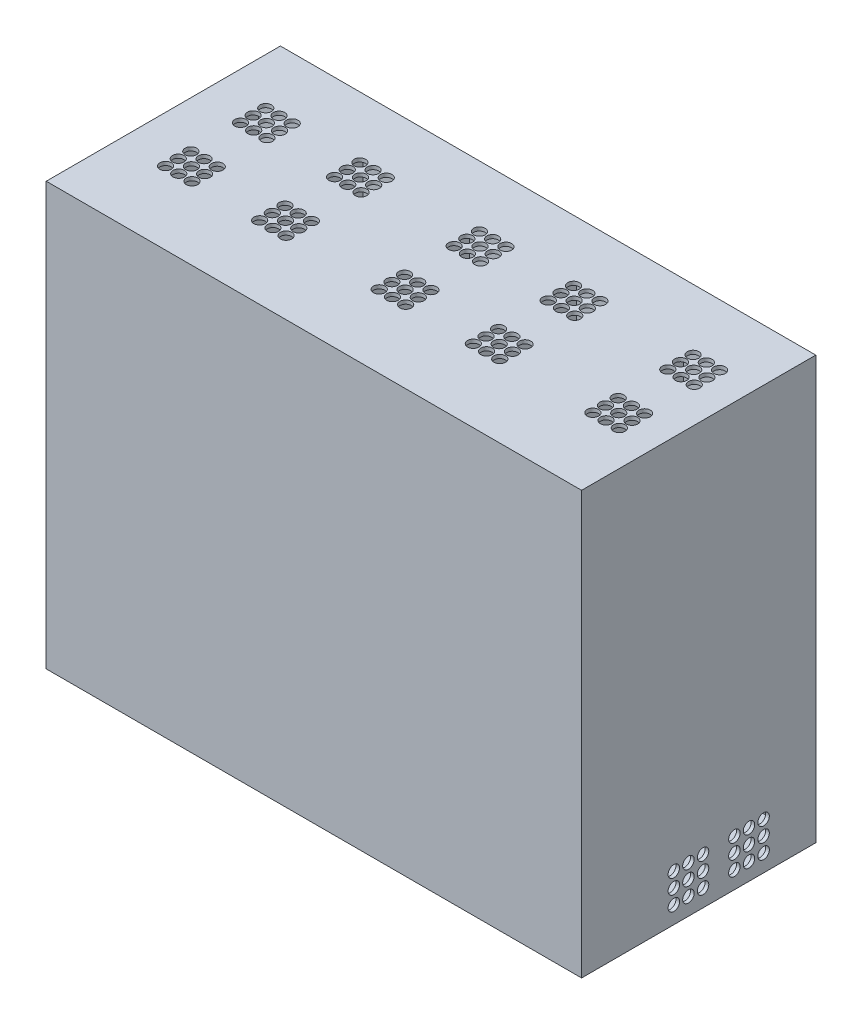
SolidWorks part; units mm, degrees
material "6061-T6 (SS)"
ref_plane "X-Y Datum" through (0, 0, 0) normal (0, 0, 1) x (1, 0, 0)
ref_plane "X-Z Datum" through (0, 0, 0) normal (0, 1, 0) x (1, 0, 0)
ref_plane "Y-Z Datum" through (0, 0, 0) normal (1, 0, 0) x (0, 0, -1)
sketch "Sketch1" plane through (0, 0, 0) normal (0, 0, 1) x (1, 0, 0)
  line L0 (-276.2265, 0) -> (276.2265, 0) construction
  line L1 (-276.2265, 154.041) -> (276.2265, 154.041)
  line L2 (-276.2265, 154.041) -> (-276.2265, -154.041)
  line L3 (-276.2265, -154.041) -> (276.2265, -154.041)
  line L4 (276.2265, 154.041) -> (276.2265, -154.041)
  line L5 (-276.2265, 154.041) -> (276.2265, -154.041) construction
  line L6 (-276.2265, -154.041) -> (276.2265, 154.041) construction
  line L7 (-275.2105, 153.025) -> (-189.6105, 153.025) construction
  line L8 (-275.2105, 153.025) -> (-275.2105, -153.025) construction
  line L9 (-275.2105, -153.025) -> (-189.6105, -153.025) construction
  line L10 (-189.6105, 153.025) -> (-189.6105, -153.025) construction
  line L11 (-275.2105, 153.025) -> (-189.6105, -153.025) construction
  line L12 (-275.2105, -153.025) -> (-189.6105, 153.025) construction
  line L13 (-188.5945, -154.041) -> (-188.5945, 154.041)
  line L14 (-279.4015, 157.216) -> (279.4015, 157.216)
  line L15 (279.4015, 157.216) -> (279.4015, -157.216)
  line L16 (-279.4015, -157.216) -> (279.4015, -157.216)
  line L17 (-279.4015, 157.216) -> (-279.4015, -157.216)
  line L18 (-185.4195, -154.041) -> (-185.4195, 154.041)
  line L19 (-188.5945, 0) -> (-185.4195, 0) construction
  line L20 (-182.2465, 153.025) -> (-182.2465, -153.025) construction
  line L21 (-182.2465, 153.025) -> (-96.6465, 153.025) construction
  line L22 (-96.6465, 153.025) -> (-96.6465, -153.025) construction
  line L23 (-182.2465, -153.025) -> (-96.6465, -153.025) construction
  line L24 (-95.6305, -154.041) -> (-95.6305, 154.041)
  line L25 (-92.4555, -154.041) -> (-92.4555, 154.041)
  line L26 (-89.2825, 153.025) -> (-89.2825, -153.025) construction
  line L27 (-89.2825, 153.025) -> (-3.6825, 153.025) construction
  line L28 (-3.6825, 153.025) -> (-3.6825, -153.025) construction
  line L29 (-89.2825, -153.025) -> (-3.6825, -153.025) construction
  line L30 (-2.6665, -154.041) -> (-2.6665, 154.041)
  line L31 (0.5085, -154.041) -> (0.5085, 154.041)
  line L32 (3.6815, 153.025) -> (3.6815, -153.025) construction
  line L33 (3.6815, 153.025) -> (89.2815, 153.025) construction
  line L34 (89.2815, 153.025) -> (89.2815, -153.025) construction
  line L35 (3.6815, -153.025) -> (89.2815, -153.025) construction
  line L36 (90.2975, -154.041) -> (90.2975, 154.041)
  line L37 (93.4725, -154.041) -> (93.4725, 154.041)
  line L38 (96.6455, 153.025) -> (96.6455, -153.025) construction
  line L39 (96.6455, 153.025) -> (182.2455, 153.025) construction
  line L40 (182.2455, 153.025) -> (182.2455, -153.025) construction
  line L41 (96.6455, -153.025) -> (182.2455, -153.025) construction
  line L42 (183.2615, -154.041) -> (183.2615, 154.041)
  line L43 (186.4365, -154.041) -> (186.4365, 154.041)
  line L44 (-182.2465, -153.025) -> (-96.6465, 153.025) construction
  line L45 (-182.2465, 153.025) -> (-96.6465, -153.025) construction
  line L46 (-89.2825, -153.025) -> (-3.6825, 153.025) construction
  line L47 (-89.2825, 153.025) -> (-3.6825, -153.025) construction
  line L48 (3.6815, -153.025) -> (89.2815, 153.025) construction
  line L49 (3.6815, 153.025) -> (89.2815, -153.025) construction
  line L50 (96.6455, -153.025) -> (182.2455, 153.025) construction
  line L51 (96.6455, 153.025) -> (182.2455, -153.025) construction
  line L52 (-276.2265, -157.216) -> (-276.2265, -208.016)
  line L53 (-279.4015, -157.216) -> (279.4015, -157.216)
  line L54 (-279.4015, -157.216) -> (-279.4015, -210.302)
  line L56 (279.4015, -157.216) -> (279.4015, -397.1906)
  line L58 (276.2265, -157.216) -> (276.2265, -392.7808)
  line L59 (186.4365, -154.041) -> (186.4365, -210.302)
  line L60 (183.2615, -157.216) -> (183.2615, -208.016)
  line L61 (186.4365, 154.041) -> (186.4365, 157.216)
  line L62 (-276.2265, -208.016) -> (276.2265, -392.7808) construction
  line L63 (-276.2265, -208.016) -> (183.2615, -208.016)
  line L64 (-279.4015, -210.302) -> (186.4365, -210.302)
  line L65 (-279.4015, -210.302) -> (279.4015, -397.1906) construction
  point P0 (0, 0)
  point P6 (-232.4105, 0)
  point P23 (-187.007, 0)
  point P24 (-139.4465, 0)
  dimension "D1" = 306.05
  dimension "D2" = 85.6
  dimension "D3" = 1.016
  dimension "D4" = 1.016
  dimension "D5" = 1.016
  dimension "D8" = 45.4035
  dimension "D10" = 89.789
  dimension "D12" = 92.964
  dimension "D13" = 89.79
  dimension "D14" = 50.8
  dimension "D16" = 2.286
  dimension "D6" = 3.175
  dimension "D7" = 3.175
  dimension "D15" = 3.175
  dimension "D9" = 5
  dimension "D11" = 5
extrude "Boss-Extrude1" add sketch "Sketch1" along normal blind 3.175 contours L3 L43 L1 L42 | L54 L64 L59 L53 L60 L63 L52 L16 | L52 L63 L60 L16 | L3 L42 L1 L37 | L3 L36 L1 L31 | L3 L31 L1 L30 | L3 L37 L1 L36 | L3 L30 L1 L25 | L1 L61 L14 L17 L16 L53 L59 L3 L2 | L3 L24 L1 L18 | L3 L13 L1 L2 | L3 L18 L1 L13 | L3 L25 L1 L24 region at (-276.7885, 0, 0) region at (-232.4105, 0, 0) region at (-187.007, 0, 0) region at (-140.525, 0, 0) region at (-94.043, 0, 0) region at (-47.561, 0, 0) region at (-1.079, 0, 0) region at (45.403, 0, 0) region at (91.885, 0, 0) region at (138.367, 0, 0) region at (184.849, 0, 0) region at (185.9676, -183.759, 0) region at (-46.4825, -182.616, 0)
sketch "Sketch2" plane through (0, 0, 3.175) normal (0, 0, 1) x (1, 0, 0)
  line L0 (-188.5945, -154.041) -> (-188.5945, 154.041) construction
  line L1 (-95.6305, -154.041) -> (-95.6305, 154.041) construction
  line L2 (-185.4195, -154.041) -> (-185.4195, 154.041) construction
  line L3 (90.2975, -154.041) -> (90.2975, 154.041) construction
  line L4 (276.2265, 154.041) -> (-276.2265, 154.041)
  line L5 (276.2265, -154.041) -> (276.2265, 154.041)
  line L6 (-276.2265, -154.041) -> (276.2265, -154.041)
  line L7 (-276.2265, 154.041) -> (-276.2265, -154.041)
  line L8 (276.2265, 154.041) -> (-276.2265, 154.041)
  line L9 (276.2265, -154.041) -> (276.2265, 154.041)
  line L10 (-276.2265, -154.041) -> (276.2265, -154.041)
  line L11 (-276.2265, 154.041) -> (-276.2265, -154.041)
  line L12 (-279.4015, -157.216) -> (279.4015, -157.216)
  line L13 (-279.4015, -157.216) -> (279.4015, -157.216) construction
  line L14 (279.4015, 157.216) -> (279.4015, -157.216) construction
  line L15 (-279.4015, 157.216) -> (279.4015, 157.216) construction
  line L16 (-279.4015, -157.216) -> (279.4015, -157.216)
  line L20 (0.5085, -154.041) -> (0.5085, 154.041) construction
  line L21 (-2.6665, -154.041) -> (-2.6665, 154.041) construction
  line L22 (-92.4555, -154.041) -> (-92.4555, 154.041) construction
  line L23 (186.4365, -154.041) -> (186.4365, 154.041) construction
  line L24 (183.2615, -154.041) -> (183.2615, 154.041) construction
  line L25 (93.4725, -154.041) -> (93.4725, 154.041) construction
  line L26 (-188.5945, -154.041) -> (-188.5945, 154.041)
  line L27 (-95.6305, -154.041) -> (-95.6305, 154.041)
  line L28 (-185.4195, -154.041) -> (-185.4195, 154.041)
  line L29 (90.2975, -154.041) -> (90.2975, 154.041)
  line L30 (0.5085, -154.041) -> (0.5085, 154.041)
  line L31 (-2.6665, -154.041) -> (-2.6665, 154.041)
  line L32 (-92.4555, -154.041) -> (-92.4555, 154.041)
  line L33 (186.4365, -154.041) -> (186.4365, 154.041)
  line L34 (183.2615, -154.041) -> (183.2615, 154.041)
  line L35 (93.4725, -154.041) -> (93.4725, 154.041)
  line L36 (-279.4015, 157.216) -> (-279.4015, -157.216) construction
  line L37 (-279.4015, -157.216) -> (279.4015, -157.216) construction
  line L38 (-279.4015, -157.216) -> (-279.4015, -210.302) construction
  line L41 (-276.2265, -157.216) -> (-276.2265, -208.016) construction
  line L44 (-276.2265, 154.041) -> (276.2265, 154.041) construction
  line L45 (276.2265, 154.041) -> (276.2265, -154.041) construction
  line L46 (-276.2265, -154.041) -> (276.2265, -154.041) construction
  line L47 (-276.2265, 154.041) -> (-276.2265, -154.041) construction
  line L48 (-188.5945, -154.041) -> (-188.5945, 154.041)
  line L49 (-95.6305, -154.041) -> (-95.6305, 154.041)
  line L50 (-185.4195, -154.041) -> (-185.4195, 154.041)
  line L51 (-279.4015, -157.216) -> (279.4015, -157.216)
  line L52 (279.4015, 157.216) -> (279.4015, -157.216)
  line L53 (-279.4015, 157.216) -> (279.4015, 157.216)
  line L54 (-279.4015, 157.216) -> (-279.4015, -157.216)
  line L55 (-279.4015, -157.216) -> (279.4015, -157.216)
  line L56 (-279.4015, -157.216) -> (-279.4015, -210.302)
  line L59 (90.2975, -154.041) -> (90.2975, 154.041)
  line L60 (0.5085, -154.041) -> (0.5085, 154.041)
  line L61 (-2.6665, -154.041) -> (-2.6665, 154.041)
  line L62 (-92.4555, -154.041) -> (-92.4555, 154.041)
  line L63 (186.4365, -154.041) -> (186.4365, 154.041)
  line L64 (183.2615, -154.041) -> (183.2615, 154.041)
  line L65 (93.4725, -154.041) -> (93.4725, 154.041)
  line L66 (-276.2265, -157.216) -> (-276.2265, -208.016)
  line L67 (-279.4015, -210.302) -> (186.4365, -210.302) construction
  line L69 (-276.2265, 154.041) -> (276.2265, 154.041)
  line L70 (276.2265, 154.041) -> (276.2265, -154.041)
  line L71 (-276.2265, -154.041) -> (276.2265, -154.041)
  line L72 (-276.2265, 154.041) -> (-276.2265, -154.041)
  line L73 (183.2615, -157.216) -> (183.2615, -208.016) construction
  line L74 (186.4365, 154.041) -> (186.4365, 157.216) construction
  line L75 (186.4365, -154.041) -> (186.4365, -210.302) construction
  line L76 (-188.5945, -154.041) -> (-188.5945, 154.041)
  line L77 (-95.6305, -154.041) -> (-95.6305, 154.041)
  line L78 (-185.4195, -154.041) -> (-185.4195, 154.041)
  line L79 (-279.4015, -157.216) -> (279.4015, -157.216)
  line L80 (279.4015, 157.216) -> (279.4015, -157.216)
  line L81 (-279.4015, 157.216) -> (279.4015, 157.216)
  line L82 (-279.4015, 157.216) -> (-279.4015, -157.216)
  line L83 (-279.4015, -157.216) -> (279.4015, -157.216)
  line L84 (-279.4015, -157.216) -> (-279.4015, -210.302)
  line L85 (-276.2265, -208.016) -> (183.2615, -208.016) construction
  line L87 (90.2975, -154.041) -> (90.2975, 154.041)
  line L88 (0.5085, -154.041) -> (0.5085, 154.041)
  line L89 (-2.6665, -154.041) -> (-2.6665, 154.041)
  line L90 (-92.4555, -154.041) -> (-92.4555, 154.041)
  line L91 (183.2615, -154.041) -> (183.2615, 154.041)
  line L92 (93.4725, -154.041) -> (93.4725, 154.041)
  line L93 (183.2615, -157.216) -> (183.2615, -208.016)
  line L94 (-276.2265, -157.216) -> (-276.2265, -208.016)
  line L97 (186.4365, 154.041) -> (186.4365, 157.216)
  line L98 (186.4365, -154.041) -> (186.4365, 154.041)
  line L99 (186.4365, -154.041) -> (186.4365, -210.302)
  line L100 (-276.2265, 154.041) -> (276.2265, 154.041)
  line L101 (276.2265, 154.041) -> (276.2265, -154.041)
  line L102 (-276.2265, -154.041) -> (276.2265, -154.041)
  line L103 (-276.2265, 154.041) -> (-276.2265, -154.041)
  line L104 (-188.5945, -154.041) -> (-188.5945, 154.041)
  line L106 (-95.6305, -154.041) -> (-95.6305, 154.041)
  line L107 (-185.4195, -154.041) -> (-185.4195, 154.041)
  line L108 (-279.4015, -157.216) -> (279.4015, -157.216)
  line L109 (279.4015, 157.216) -> (279.4015, -157.216)
  line L110 (-279.4015, 157.216) -> (279.4015, 157.216)
  line L111 (-279.4015, 157.216) -> (-279.4015, -157.216)
  line L112 (-279.4015, -157.216) -> (279.4015, -157.216)
  line L113 (186.4365, 154.041) -> (186.4365, 157.216)
  line L114 (186.4365, -154.041) -> (186.4365, 154.041)
  line L115 (186.4365, -154.041) -> (186.4365, -210.302)
  line L116 (-279.4015, -210.302) -> (186.4365, -210.302)
  line L117 (-279.4015, -157.216) -> (-279.4015, -210.302)
  line L118 (90.2975, -154.041) -> (90.2975, 154.041)
  line L119 (0.5085, -154.041) -> (0.5085, 154.041)
  line L120 (-2.6665, -154.041) -> (-2.6665, 154.041)
  line L121 (-92.4555, -154.041) -> (-92.4555, 154.041)
  line L122 (183.2615, -154.041) -> (183.2615, 154.041)
  line L123 (93.4725, -154.041) -> (93.4725, 154.041)
  line L124 (183.2615, -157.216) -> (183.2615, -208.016)
  line L125 (-276.2265, -208.016) -> (183.2615, -208.016)
  line L126 (-276.2265, -157.216) -> (-276.2265, -208.016)
  line L128 (-276.2265, 154.041) -> (276.2265, 154.041)
  line L129 (276.2265, 154.041) -> (276.2265, -154.041)
  line L130 (-276.2265, -154.041) -> (276.2265, -154.041)
  line L131 (-276.2265, 154.041) -> (-276.2265, -154.041)
  line M9 (186.4365, 157.216) -> (-279.4015, 157.216)
  line M10 (-279.4015, 157.216) -> (-279.4015, -210.302)
  line M86 (186.4365, -210.302) -> (186.4365, 157.216)
  line M120 (-279.4015, -210.302) -> (186.4365, -210.302)
  dimension "D1" = 0
  dimension "D2" = 0
extrude "Boss-Extrude2" add sketch "Sketch2" along normal blind 200.6 contours L125 L66 L16 L83 L93 M10 M120 M86 | L16 L55 L83 L10 L11 L8 M10 M86 M9 | L34 L10 L8 M86 | L10 L35 L8 L29 | L10 L28 L8 L26 | L10 L32 L8 L27 | L31 L10 L30 L8 region at (184.849, 0, 3.175) region at (184.849, 154.603, 3.175) region at (91.885, 0, 3.175) region at (185.9676, -183.759, 3.175) region at (-1.079, 0, 3.175) region at (-94.043, 0, 3.175) region at (-187.007, 0, 3.175)
sketch "Sketch11" plane through (0, 0, 203.775) normal (0, 0, 1) x (1, 0, 0)
  line L0 (-188.5945, -154.041) -> (-188.5945, 154.041) construction
  line L2 (-95.6305, -154.041) -> (-95.6305, 154.041) construction
  line L3 (-185.4195, -154.041) -> (-185.4195, 154.041) construction
  line L4 (186.4365, -210.302) -> (186.4365, 157.216)
  line L5 (186.4365, 157.216) -> (-279.4015, 157.216)
  line L6 (-279.4015, 157.216) -> (-279.4015, -210.302)
  line L7 (-279.4015, -210.302) -> (186.4365, -210.302)
  line L8 (186.4365, -210.302) -> (186.4365, 157.216)
  line L9 (186.4365, 157.216) -> (-279.4015, 157.216)
  line L10 (-279.4015, 157.216) -> (-279.4015, -210.302)
  line L11 (-279.4015, -210.302) -> (186.4365, -210.302)
  line L12 (-279.4015, -157.216) -> (279.4015, -157.216) construction
  line L14 (-279.4015, 157.216) -> (279.4015, 157.216) construction
  line L15 (-279.4015, 157.216) -> (-279.4015, -157.216) construction
  line L16 (-279.4015, -157.216) -> (279.4015, -157.216) construction
  line L17 (186.4365, 154.041) -> (186.4365, 157.216) construction
  line L18 (186.4365, -154.041) -> (186.4365, 154.041) construction
  line L19 (186.4365, -154.041) -> (186.4365, -210.302) construction
  line L20 (-279.4015, -210.302) -> (186.4365, -210.302) construction
  line L21 (-279.4015, -157.216) -> (-279.4015, -210.302) construction
  line L22 (90.2975, -154.041) -> (90.2975, 154.041) construction
  line L23 (0.5085, -154.041) -> (0.5085, 154.041) construction
  line L24 (-2.6665, -154.041) -> (-2.6665, 154.041) construction
  line L25 (-92.4555, -154.041) -> (-92.4555, 154.041) construction
  line L26 (183.2615, -154.041) -> (183.2615, 154.041) construction
  line L27 (93.4725, -154.041) -> (93.4725, 154.041) construction
  line L28 (183.2615, -157.216) -> (183.2615, -208.016) construction
  line L29 (-276.2265, -208.016) -> (183.2615, -208.016) construction
  line L30 (-276.2265, -157.216) -> (-276.2265, -208.016) construction
  line L32 (-276.2265, 154.041) -> (276.2265, 154.041) construction
  line L34 (-276.2265, -154.041) -> (276.2265, -154.041) construction
  line L35 (-276.2265, 154.041) -> (-276.2265, -154.041) construction
  line L36 (-188.5945, -154.041) -> (-188.5945, 154.041)
  line L37 (183.2615, -157.216) -> (183.2615, -154.041)
  line L38 (-95.6305, -154.041) -> (-95.6305, 154.041)
  line L39 (-185.4195, -154.041) -> (-185.4195, 154.041)
  line L40 (-279.4015, -157.216) -> (186.4365, -157.216)
  line L42 (-279.4015, 157.216) -> (186.4365, 157.216)
  line L43 (-279.4015, 157.216) -> (-279.4015, -157.216)
  line L44 (-279.4015, -157.216) -> (186.4365, -157.216)
  line L45 (186.4365, 154.041) -> (186.4365, 157.216)
  line L46 (186.4365, -154.041) -> (186.4365, 154.041)
  line L47 (186.4365, -154.041) -> (186.4365, -210.302)
  line L48 (-279.4015, -210.302) -> (186.4365, -210.302)
  line L49 (-279.4015, -157.216) -> (-279.4015, -210.302)
  line L50 (90.2975, -154.041) -> (90.2975, 154.041)
  line L51 (0.5085, -154.041) -> (0.5085, 154.041)
  line L52 (-2.6665, -154.041) -> (-2.6665, 154.041)
  line L53 (-92.4555, -154.041) -> (-92.4555, 154.041)
  line L54 (183.2615, -154.041) -> (183.2615, 154.041)
  line L55 (93.4725, -154.041) -> (93.4725, 154.041)
  line L56 (183.2615, -157.216) -> (183.2615, -208.016)
  line L57 (-276.2265, -208.016) -> (183.2615, -208.016)
  line L58 (-276.2265, -157.216) -> (-276.2265, -208.016)
  line L59 (-276.2265, -157.216) -> (-276.2265, -154.041)
  line L60 (-276.2265, 154.041) -> (186.4365, 154.041)
  line L62 (-276.2265, -154.041) -> (186.4365, -154.041)
  line L63 (-276.2265, 154.041) -> (-276.2265, -154.041)
  line M7 (-185.4195, 154.041) -> (-95.6305, 154.041)
  line M11 (-92.4555, 154.041) -> (-2.6665, 154.041)
  line M15 (0.5085, 154.041) -> (90.2975, 154.041)
  line M19 (93.4725, 154.041) -> (183.2615, 154.041)
  line M20 (183.2615, 154.041) -> (183.2615, -154.041)
  line M21 (186.4365, -210.302) -> (186.4365, 157.216)
  line M22 (186.4365, 157.216) -> (-279.4015, 157.216)
  line M23 (-279.4015, 157.216) -> (-279.4015, -210.302)
  line M24 (-279.4015, -210.302) -> (186.4365, -210.302)
  line M25 (-276.2265, -208.016) -> (-276.2265, -157.216)
  line M27 (183.2615, -157.216) -> (183.2615, -208.016)
  line M28 (183.2615, -208.016) -> (-276.2265, -208.016)
  line M31 (-276.2265, -154.041) -> (-276.2265, 154.041)
  line M32 (-276.2265, 154.041) -> (-188.5945, 154.041)
  dimension "D1" = 0
extrude "Boss-Extrude8" add sketch "Sketch11" along normal blind 64.05 contours L40 L10 M24 M21 M27 M28 M25 | L62 L60 M20 M21 | L62 L37 L40 L8 | L60 L40 L59 M32 M7 M11 M15 M19 M21 M22 M23 M31 region at (-46.4825, -209.8331, 203.775) region at (184.849, -155.6285, 203.775) region at (184.849, 0, 203.775) region at (-278.8395, 0, 203.775)
sketch "Sketch10" plane through (0, 0, 0) normal (0, 0, 1) x (1, 0, 0)
  line L1 (186.4365, 157.216) -> (220.4725, 157.216)
  line L2 (186.4365, 157.216) -> (186.4365, 61.966)
  line L3 (186.4365, 61.966) -> (220.4725, 61.966)
  line L4 (186.4365, -210.302) -> (186.4365, 157.216)
  line L5 (-279.4015, -210.302) -> (186.4365, -210.302)
  line L6 (-279.4015, 157.216) -> (-279.4015, -210.302)
  line L7 (186.4365, 157.216) -> (-279.4015, 157.216)
  line L8 (186.4365, -210.302) -> (186.4365, 157.216)
  line L10 (-279.4015, 157.216) -> (-279.4015, -210.302)
  line L11 (186.4365, 157.216) -> (-279.4015, 157.216)
  line L12 (220.4725, 157.216) -> (220.4725, 61.966)
  line L13 (-276.2265, -157.216) -> (183.2615, -157.216) construction
  line L14 (-276.2265, -157.216) -> (183.2615, -157.216)
  line L15 (186.4365, -157.216) -> (220.4725, -157.216)
  line L16 (186.4365, -157.216) -> (186.4365, -61.966)
  line L17 (186.4365, -61.966) -> (220.4725, -61.966)
  line L18 (220.4725, -157.216) -> (220.4725, -61.966)
  line L19 (186.4365, 157.216) -> (135.6365, 157.216)
  line L20 (186.4365, 157.216) -> (186.4365, 191.252)
  line L21 (186.4365, 191.252) -> (135.6365, 191.252)
  line L22 (135.6365, 157.216) -> (135.6365, 191.252)
  line L26 (-279.4015, -210.302) -> (186.4365, -210.302)
  dimension "D2" = 34.036
  dimension "D3" = 95.25
  dimension "D4" = 50.8
  dimension "D1" = 0
extrude "Boss-Extrude7" add sketch "Sketch10" along normal blind 3.175 contours L12 L1 L2 L3 | L15 L18 L17 L8 | L22 L11 L20 L21 region at (203.4545, 109.591, 0) region at (161.0365, 174.234, 0) region at (203.4545, -109.591, 0)
ref_plane "Plane1" through (-46.4825, 0, 0) normal (-1, 0, 0) x (0, 0, 1)
mirror "Mirror1" [suppressed] about plane through (-46.4825, 0, 0) normal (-1, 0, 0)
sketch "Sketch12" plane through (186.4365, 0, 0) normal (1, 0, 0) x (0, 0, -1)
  line L0 (-223.375, -210.302) -> (-267.825, -108.702)
  line L1 (-267.825, 93.716) -> (-242.425, 157.216)
  line L10 (0, -210.302) -> (0, -157.216)
  line L13 (0, -157.216) -> (-3.175, -157.216)
  line L14 (0, -157.216) -> (-3.175, -157.216)
  line L15 (-3.175, -157.216) -> (-3.175, -61.966)
  line L16 (-3.175, -157.216) -> (-3.175, -61.966)
  line L17 (-3.175, 157.216) -> (-267.825, 157.216)
  line L18 (-267.825, 157.216) -> (-267.825, -210.302)
  line L19 (-267.825, -210.302) -> (0, -210.302)
  line L20 (0, -210.302) -> (0, -157.216)
  line L27 (-3.175, 157.216) -> (-267.825, 157.216)
  line L28 (-267.825, 157.216) -> (-267.825, -210.302)
  line L29 (-267.825, -210.302) -> (0, -210.302)
  line L30 (-3.175, -61.966) -> (0, -61.966)
  line L31 (-3.175, -61.966) -> (0, -61.966)
  line L32 (0, -61.966) -> (0, 61.966)
  line L33 (0, -61.966) -> (0, 61.966)
  line L34 (0, 61.966) -> (-3.175, 61.966)
  line L35 (0, 61.966) -> (-3.175, 61.966)
  line L36 (-3.175, 61.966) -> (-3.175, 157.216)
  line L37 (-3.175, 61.966) -> (-3.175, 157.216)
  line M18 (-3.175, 157.216) -> (-267.825, 157.216)
  line M19 (-267.825, 157.216) -> (-267.825, -210.302)
  line M20 (-267.825, -210.302) -> (0, -210.302)
  dimension "D2" = 44.45
  dimension "D3" = 101.6
  dimension "D4" = 25.4
  dimension "D5" = 63.5
  dimension "D1" = 0
extrude "Cut-Extrude1" cut sketch "Sketch12" against normal through all contours L0 M20 M19 | L1 M19 M18 region at (186.4365, -176.4353, 253.0083) region at (186.4365, 136.0493, 259.3583)
sketch "Sketch13" plane through (0, 157.216, 0) normal (0, 1, 0) x (1, 0, 0)
  circle A0 centre (-238.9105, -118.4317) radius 5 construction
  circle A1 centre (-238.9105, -129.4317) radius 5 construction
  circle A2 centre (-238.9105, -140.4317) radius 5 construction
  circle A3 centre (-227.4105, -140.4317) radius 5 construction
  circle A4 centre (-227.4105, -129.4317) radius 5 construction
  circle A5 centre (-227.4105, -118.4317) radius 5 construction
  circle A6 centre (-215.9105, -118.4317) radius 5 construction
  circle A7 centre (-215.9105, -129.4317) radius 5 construction
  circle A8 centre (-215.9105, -140.4317) radius 5 construction
  circle A9 centre (-238.9105, -118.4317) radius 5
  circle A10 centre (-238.9105, -129.4317) radius 5
  circle A11 centre (-238.9105, -140.4317) radius 5
  circle A12 centre (-227.4105, -140.4317) radius 5
  circle A13 centre (-227.4105, -129.4317) radius 5
  circle A14 centre (-227.4105, -118.4317) radius 5
  circle A15 centre (-215.9105, -118.4317) radius 5
  circle A16 centre (-215.9105, -129.4317) radius 5
  circle A17 centre (-215.9105, -140.4317) radius 5
  circle A18 centre (-215.9105, -53.2317) radius 5 construction
  circle A19 centre (-215.9105, -53.2317) radius 5
  circle A20 centre (-215.9105, -75.2317) radius 5 construction
  circle A21 centre (-227.4105, -75.2317) radius 5 construction
  circle A22 centre (-238.9105, -75.2317) radius 5 construction
  circle A23 centre (-238.9105, -64.2317) radius 5 construction
  circle A24 centre (-227.4105, -64.2317) radius 5 construction
  circle A25 centre (-215.9105, -64.2317) radius 5 construction
  circle A26 centre (-227.4105, -53.2317) radius 5 construction
  circle A27 centre (-238.9105, -53.2317) radius 5 construction
  circle A28 centre (-215.9105, -75.2317) radius 5
  circle A29 centre (-227.4105, -75.2317) radius 5
  circle A30 centre (-238.9105, -75.2317) radius 5
  circle A31 centre (-238.9105, -64.2317) radius 5
  circle A32 centre (-227.4105, -64.2317) radius 5
  circle A33 centre (-215.9105, -64.2317) radius 5
  circle A34 centre (-215.9105, -53.2317) radius 5
  circle A35 centre (-227.4105, -53.2317) radius 5
  circle A36 centre (-238.9105, -53.2317) radius 5
  circle A37 centre (-145.525, -140.4317) radius 5 construction
  circle A38 centre (-145.525, -129.4317) radius 5 construction
  circle A39 centre (-145.525, -118.4317) radius 5 construction
  circle A40 centre (-157.025, -118.4317) radius 5 construction
  circle A41 centre (-157.025, -129.4317) radius 5 construction
  circle A42 centre (-157.025, -140.4317) radius 5 construction
  circle A43 centre (-145.525, -140.4317) radius 5
  circle A44 centre (-145.525, -129.4317) radius 5
  circle A45 centre (-145.525, -118.4317) radius 5
  circle A46 centre (-157.025, -118.4317) radius 5
  circle A47 centre (-157.025, -129.4317) radius 5
  circle A48 centre (-157.025, -140.4317) radius 5
  circle A49 centre (-134.025, -118.4317) radius 5 construction
  circle A50 centre (-134.025, -140.4317) radius 5 construction
  circle A51 centre (-134.025, -129.4317) radius 5 construction
  circle A52 centre (-134.025, -118.4317) radius 5
  circle A53 centre (-134.025, -140.4317) radius 5
  circle A54 centre (-134.025, -129.4317) radius 5
  circle A55 centre (-157.025, -75.2317) radius 5 construction
  circle A56 centre (-145.525, -75.2317) radius 5 construction
  circle A57 centre (-134.025, -75.2317) radius 5 construction
  circle A58 centre (-157.025, -75.2317) radius 5
  circle A59 centre (-145.525, -75.2317) radius 5
  circle A60 centre (-134.025, -75.2317) radius 5
  circle A61 centre (-134.025, -53.2317) radius 5 construction
  circle A62 centre (-145.525, -53.2317) radius 5 construction
  circle A63 centre (-157.025, -53.2317) radius 5 construction
  circle A64 centre (-157.025, -64.2317) radius 5 construction
  circle A65 centre (-134.025, -64.2317) radius 5 construction
  circle A66 centre (-145.525, -64.2317) radius 5 construction
  circle A67 centre (-134.025, -53.2317) radius 5
  circle A68 centre (-145.525, -53.2317) radius 5
  circle A69 centre (-157.025, -53.2317) radius 5
  circle A70 centre (-157.025, -64.2317) radius 5
  circle A71 centre (-134.025, -64.2317) radius 5
  circle A72 centre (-145.525, -64.2317) radius 5
extrude "Cut-Extrude2" cut sketch "Sketch13" against normal up to surface (3.175 mm away) contours A35 | A36 | A31 | A32 | A33 | A30 | A29 | A28 | A10 | A13 | A11 | A12 | A17 | A16 | A15 | A19 | A9 | A14 region at (-238.9105, 157.216, 129.4317) region at (-238.9105, 157.216, 140.4317) region at (-227.4105, 157.216, 140.4317) region at (-227.4105, 157.216, 129.4317) region at (-215.9105, 157.216, 118.4317) region at (-215.9105, 157.216, 129.4317) region at (-215.9105, 157.216, 140.4317) region at (-215.9105, 157.216, 75.2317) region at (-227.4105, 157.216, 75.2317) region at (-238.9105, 157.216, 75.2317) region at (-238.9105, 157.216, 64.2317) region at (-227.4105, 157.216, 64.2317) region at (-215.9105, 157.216, 64.2317) region at (-227.4105, 157.216, 53.2317) region at (-238.9105, 157.216, 53.2317) up to face at (-47.3453, 154.041, 107.467)
pattern_linear "LPattern1" count 3 spacing 185.92 along (1, 0, 0) of "Cut-Extrude2"
sketch "Sketch14" plane through (0, 157.216, 0) normal (0, 1, 0) x (1, 0, 0)
  circle A1 centre (-215.9105, -53.2317) radius 5
  circle A2 centre (-215.9105, -53.2317) radius 5
  circle A3 centre (-215.9105, -140.4317) radius 5
  circle A4 centre (-215.9105, -140.4317) radius 5
  circle A5 centre (-215.9105, -129.4317) radius 5
  circle A6 centre (-215.9105, -129.4317) radius 5
  circle A7 centre (-215.9105, -118.4317) radius 5
  circle A8 centre (-215.9105, -118.4317) radius 5
  circle A9 centre (-227.4105, -118.4317) radius 5
  circle A10 centre (-227.4105, -118.4317) radius 5
  circle A11 centre (-227.4105, -129.4317) radius 5
  circle A12 centre (-227.4105, -129.4317) radius 5
  circle A13 centre (-227.4105, -140.4317) radius 5
  circle A14 centre (-227.4105, -140.4317) radius 5
  circle A15 centre (-238.9105, -140.4317) radius 5
  circle A16 centre (-238.9105, -140.4317) radius 5
  circle A17 centre (-238.9105, -129.4317) radius 5
  circle A18 centre (-238.9105, -129.4317) radius 5
  circle A19 centre (-238.9105, -118.4317) radius 5
  circle A20 centre (-238.9105, -118.4317) radius 5
  circle A21 centre (-227.4105, -75.2317) radius 5
  circle A22 centre (-227.4105, -75.2317) radius 5
  circle A23 centre (-215.9105, -75.2317) radius 5
  circle A24 centre (-215.9105, -75.2317) radius 5
  circle A25 centre (-238.9105, -53.2317) radius 5
  circle A26 centre (-238.9105, -53.2317) radius 5
  circle A27 centre (-227.4105, -53.2317) radius 5
  circle A28 centre (-227.4105, -53.2317) radius 5
  circle A29 centre (-215.9105, -53.2317) radius 5
  circle A30 centre (-215.9105, -53.2317) radius 5
  circle A31 centre (-215.9105, -64.2317) radius 5
  circle A32 centre (-215.9105, -64.2317) radius 5
  circle A33 centre (-227.4105, -64.2317) radius 5
  circle A34 centre (-227.4105, -64.2317) radius 5
  circle A35 centre (-238.9105, -64.2317) radius 5
  circle A36 centre (-238.9105, -64.2317) radius 5
  circle A37 centre (-238.9105, -75.2317) radius 5
  circle A38 centre (-238.9105, -75.2317) radius 5
  circle A39 centre (-134.025, -118.4317) radius 5
  circle A40 centre (-134.025, -118.4317) radius 5
  circle A41 centre (-157.025, -140.4317) radius 5
  circle A42 centre (-157.025, -140.4317) radius 5
  circle A43 centre (-157.025, -129.4317) radius 5
  circle A44 centre (-157.025, -129.4317) radius 5
  circle A45 centre (-157.025, -118.4317) radius 5
  circle A46 centre (-157.025, -118.4317) radius 5
  circle A47 centre (-145.525, -118.4317) radius 5
  circle A48 centre (-145.525, -118.4317) radius 5
  circle A49 centre (-145.525, -129.4317) radius 5
  circle A50 centre (-145.525, -129.4317) radius 5
  circle A51 centre (-145.525, -140.4317) radius 5
  circle A52 centre (-145.525, -140.4317) radius 5
  circle A53 centre (-134.025, -75.2317) radius 5
  circle A54 centre (-134.025, -75.2317) radius 5
  circle A55 centre (-145.525, -75.2317) radius 5
  circle A56 centre (-145.525, -75.2317) radius 5
  circle A57 centre (-157.025, -75.2317) radius 5
  circle A58 centre (-157.025, -75.2317) radius 5
  circle A59 centre (-134.025, -129.4317) radius 5
  circle A60 centre (-134.025, -129.4317) radius 5
  circle A61 centre (-134.025, -140.4317) radius 5
  circle A62 centre (-134.025, -140.4317) radius 5
  circle A63 centre (-145.525, -64.2317) radius 5
  circle A64 centre (-145.525, -64.2317) radius 5
  circle A65 centre (-134.025, -64.2317) radius 5
  circle A66 centre (-134.025, -64.2317) radius 5
  circle A67 centre (-157.025, -64.2317) radius 5
  circle A68 centre (-157.025, -64.2317) radius 5
  circle A69 centre (-157.025, -53.2317) radius 5
  circle A70 centre (-157.025, -53.2317) radius 5
  circle A71 centre (-145.525, -53.2317) radius 5
  circle A72 centre (-145.525, -53.2317) radius 5
  circle A73 centre (-134.025, -53.2317) radius 5
  circle A74 centre (-134.025, -53.2317) radius 5
  dimension "D1" = 0
  dimension "D2" = 0
  dimension "D3" = 0
  dimension "D4" = 0
  dimension "D5" = 0
  dimension "D6" = 0
  dimension "D7" = 0
  dimension "D8" = 0
  dimension "D9" = 0
  dimension "D10" = 0
  dimension "D11" = 0
  dimension "D12" = 0
  dimension "D13" = 0
  dimension "D14" = 0
  dimension "D15" = 0
  dimension "D16" = 0
  dimension "D17" = 0
  dimension "D18" = 0
  dimension "D19" = 0
  dimension "D20" = 0
  dimension "D21" = 0
  dimension "D22" = 0
  dimension "D23" = 0
  dimension "D24" = 0
  dimension "D25" = 0
  dimension "D26" = 0
  dimension "D27" = 0
  dimension "D28" = 0
  dimension "D29" = 0
  dimension "D30" = 0
  dimension "D31" = 0
  dimension "D32" = 0
  dimension "D33" = 0
  dimension "D34" = 0
  dimension "D35" = 0
  dimension "D36" = 0
  dimension "D37" = 0
extrude "Cut-Extrude3" cut sketch "Sketch14" against normal up to surface (3.175 mm away) contours A42 | A52 | A62 | A60 | A50 | A44 | A46 | A48 | A40 | A56 | A54 | A66 | A64 | A68 | A70 | A72 | A74 | A58 region at (-134.025, 157.216, 118.4317) region at (-157.025, 157.216, 140.4317) region at (-157.025, 157.216, 129.4317) region at (-157.025, 157.216, 118.4317) region at (-145.525, 157.216, 118.4317) region at (-145.525, 157.216, 129.4317) region at (-145.525, 157.216, 140.4317) region at (-134.025, 157.216, 75.2317) region at (-145.525, 157.216, 75.2317) region at (-134.025, 157.216, 129.4317) region at (-134.025, 157.216, 140.4317) region at (-145.525, 157.216, 64.2317) region at (-134.025, 157.216, 64.2317) region at (-157.025, 157.216, 64.2317) region at (-157.025, 157.216, 53.2317) region at (-145.525, 157.216, 53.2317) region at (-134.025, 157.216, 53.2317) up to face at (-36.4905, 154.041, 140.4317)
pattern_linear "LPattern2" count 2 spacing 185.92 along (1, 0, 0) of "Cut-Extrude3"
sketch "Sketch16" plane through (0, -157.216, 0) normal (0, -1, 0) x (1, 0, 0)
  circle A0 centre (-215.9105, 140.4317) radius 5 construction
  circle A1 centre (-227.4105, 140.4317) radius 5 construction
  circle A2 centre (-238.9105, 140.4317) radius 5 construction
  circle A3 centre (-215.9105, 129.4317) radius 5 construction
  circle A4 centre (-238.9105, 129.4317) radius 5 construction
  circle A5 centre (-227.4105, 129.4317) radius 5 construction
  circle A6 centre (-215.9105, 118.4317) radius 5 construction
  circle A7 centre (-227.4105, 118.4317) radius 5 construction
  circle A8 centre (-238.9105, 118.4317) radius 5 construction
  circle A9 centre (-215.9105, 107.4317) radius 5 construction
  circle A10 centre (-227.4105, 107.4317) radius 5 construction
  circle A11 centre (-238.9105, 107.4317) radius 5 construction
  circle A12 centre (-215.9105, 96.4317) radius 5 construction
  circle A13 centre (-227.4105, 96.4317) radius 5 construction
  circle A14 centre (-238.9105, 96.4317) radius 5 construction
  circle A15 centre (-215.9105, 85.4317) radius 5 construction
  circle A16 centre (-227.4105, 74.4317) radius 5 construction
  circle A17 centre (-227.4105, 85.4317) radius 5 construction
  circle A18 centre (-238.9105, 85.4317) radius 5 construction
  circle A19 centre (-238.9105, 74.4317) radius 5 construction
  circle A20 centre (-227.4105, 63.4317) radius 5 construction
  circle A21 centre (-238.9105, 63.4317) radius 5 construction
  circle A22 centre (-238.9105, 52.4317) radius 5 construction
  circle A23 centre (-238.9105, 41.4317) radius 5 construction
  circle A24 centre (-238.9105, 30.4317) radius 5 construction
  circle A25 centre (-227.4105, 30.4317) radius 5 construction
  circle A26 centre (-215.9105, 30.4317) radius 5 construction
  circle A27 centre (-215.9105, 41.4317) radius 5 construction
  circle A28 centre (-227.4105, 41.4317) radius 5 construction
  circle A29 centre (-227.4105, 52.4317) radius 5 construction
  circle A30 centre (-215.9105, 52.4317) radius 5 construction
  circle A31 centre (-215.9105, 74.4317) radius 5 construction
  circle A32 centre (-215.9105, 63.4317) radius 5 construction
  circle A33 centre (-215.9105, 140.4317) radius 5
  circle A34 centre (-227.4105, 140.4317) radius 5
  circle A35 centre (-238.9105, 140.4317) radius 5
  circle A36 centre (-215.9105, 129.4317) radius 5
  circle A37 centre (-238.9105, 129.4317) radius 5
  circle A38 centre (-227.4105, 129.4317) radius 5
  circle A39 centre (-215.9105, 118.4317) radius 5
  circle A40 centre (-227.4105, 118.4317) radius 5
  circle A41 centre (-238.9105, 118.4317) radius 5
  circle A42 centre (-215.9105, 107.4317) radius 5
  circle A43 centre (-227.4105, 107.4317) radius 5
  circle A44 centre (-238.9105, 107.4317) radius 5
  circle A45 centre (-215.9105, 96.4317) radius 5
  circle A46 centre (-227.4105, 96.4317) radius 5
  circle A47 centre (-238.9105, 96.4317) radius 5
  circle A48 centre (-215.9105, 85.4317) radius 5
  circle A49 centre (-227.4105, 74.4317) radius 5
  circle A50 centre (-227.4105, 85.4317) radius 5
  circle A51 centre (-238.9105, 85.4317) radius 5
  circle A52 centre (-238.9105, 74.4317) radius 5
  circle A53 centre (-227.4105, 63.4317) radius 5
  circle A54 centre (-238.9105, 63.4317) radius 5
  circle A55 centre (-238.9105, 52.4317) radius 5
  circle A56 centre (-238.9105, 41.4317) radius 5
  circle A57 centre (-238.9105, 30.4317) radius 5
  circle A58 centre (-227.4105, 30.4317) radius 5
  circle A59 centre (-215.9105, 30.4317) radius 5
  circle A60 centre (-215.9105, 41.4317) radius 5
  circle A61 centre (-227.4105, 41.4317) radius 5
  circle A62 centre (-227.4105, 52.4317) radius 5
  circle A63 centre (-215.9105, 52.4317) radius 5
  circle A64 centre (-215.9105, 74.4317) radius 5
  circle A65 centre (-215.9105, 63.4317) radius 5
  circle A66 centre (-134.025, 140.4317) radius 5 construction
  circle A67 centre (-145.525, 140.4317) radius 5 construction
  circle A68 centre (-157.025, 140.4317) radius 5 construction
  circle A69 centre (-134.025, 129.4317) radius 5 construction
  circle A70 centre (-145.525, 129.4317) radius 5 construction
  circle A71 centre (-157.025, 129.4317) radius 5 construction
  circle A72 centre (-134.025, 118.4317) radius 5 construction
  circle A73 centre (-145.525, 118.4317) radius 5 construction
  circle A74 centre (-157.025, 118.4317) radius 5 construction
  circle A75 centre (-134.025, 107.4317) radius 5 construction
  circle A76 centre (-145.525, 107.4317) radius 5 construction
  circle A77 centre (-157.025, 107.4317) radius 5 construction
  circle A78 centre (-134.025, 96.4317) radius 5 construction
  circle A79 centre (-145.525, 96.4317) radius 5 construction
  circle A80 centre (-157.025, 96.4317) radius 5 construction
  circle A81 centre (-134.025, 85.4317) radius 5 construction
  circle A82 centre (-145.525, 85.4317) radius 5 construction
  circle A83 centre (-157.025, 85.4317) radius 5 construction
  circle A84 centre (-134.025, 74.4317) radius 5 construction
  circle A85 centre (-145.525, 74.4317) radius 5 construction
  circle A86 centre (-157.025, 74.4317) radius 5 construction
  circle A87 centre (-134.025, 63.4317) radius 5 construction
  circle A88 centre (-145.525, 63.4317) radius 5 construction
  circle A89 centre (-157.025, 63.4317) radius 5 construction
  circle A90 centre (-134.025, 52.4317) radius 5 construction
  circle A91 centre (-145.525, 52.4317) radius 5 construction
  circle A92 centre (-157.025, 52.4317) radius 5 construction
  circle A93 centre (-134.025, 41.4317) radius 5 construction
  circle A94 centre (-145.525, 41.4317) radius 5 construction
  circle A95 centre (-157.025, 41.4317) radius 5 construction
  circle A96 centre (-134.025, 30.4317) radius 5 construction
  circle A97 centre (-145.525, 30.4317) radius 5 construction
  circle A98 centre (-157.025, 30.4317) radius 5 construction
  circle A99 centre (-134.025, 140.4317) radius 5
  circle A100 centre (-145.525, 140.4317) radius 5
  circle A101 centre (-157.025, 140.4317) radius 5
  circle A102 centre (-134.025, 129.4317) radius 5
  circle A103 centre (-145.525, 129.4317) radius 5
  circle A104 centre (-157.025, 129.4317) radius 5
  circle A105 centre (-134.025, 118.4317) radius 5
  circle A106 centre (-145.525, 118.4317) radius 5
  circle A107 centre (-157.025, 118.4317) radius 5
  circle A108 centre (-134.025, 107.4317) radius 5
  circle A109 centre (-145.525, 107.4317) radius 5
  circle A110 centre (-157.025, 107.4317) radius 5
  circle A111 centre (-134.025, 96.4317) radius 5
  circle A112 centre (-145.525, 96.4317) radius 5
  circle A113 centre (-157.025, 96.4317) radius 5
  circle A114 centre (-134.025, 85.4317) radius 5
  circle A115 centre (-145.525, 85.4317) radius 5
  circle A116 centre (-157.025, 85.4317) radius 5
  circle A117 centre (-134.025, 74.4317) radius 5
  circle A118 centre (-145.525, 74.4317) radius 5
  circle A119 centre (-157.025, 74.4317) radius 5
  circle A120 centre (-134.025, 63.4317) radius 5
  circle A121 centre (-145.525, 63.4317) radius 5
  circle A122 centre (-157.025, 63.4317) radius 5
  circle A123 centre (-134.025, 52.4317) radius 5
  circle A124 centre (-145.525, 52.4317) radius 5
  circle A125 centre (-157.025, 52.4317) radius 5
  circle A126 centre (-134.025, 41.4317) radius 5
  circle A127 centre (-145.525, 41.4317) radius 5
  circle A128 centre (-157.025, 41.4317) radius 5
  circle A129 centre (-134.025, 30.4317) radius 5
  circle A130 centre (-145.525, 30.4317) radius 5
  circle A131 centre (-157.025, 30.4317) radius 5
extrude "Cut-Extrude5" cut sketch "Sketch16" against normal blind 3.175
pattern_linear "LPattern3" count 3 spacing 185.92 along (1, 0, 0) of "Cut-Extrude5"
sketch "Sketch17" plane through (-279.4015, 0, 0) normal (-1, 0, 0) x (0, 0, 1)
  line L0 (110.8, -169.916) -> (110.8, -195.316) construction
  line L1 (158.175, -182.616) -> (3.175, -182.616) construction
  line L2 (3.175, -157.216) -> (3.175, -208.016) construction
  line L3 (110.8, -162.616) -> (110.8, -202.616) construction
  line L4 (90.8, -162.616) -> (130.8, -162.616) construction
  line L5 (130.8, -202.616) -> (90.8, -202.616) construction
  line L6 (58.1, -162.616) -> (58.1, -202.616) construction
  line L7 (38.1, -162.616) -> (78.1, -162.616) construction
  line L8 (78.1, -202.616) -> (38.1, -202.616) construction
  line L9 (58.1, -169.916) -> (58.1, -195.316) construction
  circle A0 centre (110.8, -182.616) radius 5
  circle A1 centre (110.8, -169.916) radius 5
  circle A2 centre (110.8, -195.316) radius 5
  circle A3 centre (58.1, -182.616) radius 5
  circle A4 centre (58.1, -195.316) radius 5
  circle A5 centre (58.1, -169.916) radius 5
  point P5 (110.8, -182.616)
  point P27 (58.1, -182.616)
  dimension "D1" = 10
  dimension "D2" = 25.4
  dimension "D3" = 25.4
extrude "Cut-Extrude6" cut sketch "Sketch17" against normal through all
pattern_linear "LPattern4" count 2 spacing 12.7 along (0, 0, 1) count 2 spacing 12.7 along (0, 0, -1) of "Cut-Extrude6" pattern seed only yes
sketch "Sketch18" plane through (0, 0, 3.175) normal (0, 0, 1) x (1, 0, 0)
  line L0 (93.4725, -154.041) -> (183.2615, -154.041) construction
  line L1 (183.2615, -154.041) -> (183.2615, 154.041) construction
  line L2 (183.2615, 154.041) -> (93.4725, 154.041) construction
  line L3 (93.4725, 154.041) -> (93.4725, -154.041) construction
  line L4 (0.5085, -154.041) -> (90.2975, -154.041) construction
  line L5 (90.2975, -154.041) -> (90.2975, 154.041) construction
  line L6 (90.2975, 154.041) -> (0.5085, 154.041) construction
  line L7 (0.5085, 154.041) -> (0.5085, -154.041) construction
  line L8 (-92.4555, -154.041) -> (-2.6665, -154.041) construction
  line L9 (-2.6665, -154.041) -> (-2.6665, 154.041) construction
  line L10 (-2.6665, 154.041) -> (-92.4555, 154.041) construction
  line L11 (-92.4555, 154.041) -> (-92.4555, -154.041) construction
  line L12 (-185.4195, -154.041) -> (-95.6305, -154.041) construction
  line L13 (-95.6305, -154.041) -> (-95.6305, 154.041) construction
  line L14 (-95.6305, 154.041) -> (-185.4195, 154.041) construction
  line L15 (-185.4195, 154.041) -> (-185.4195, -154.041) construction
  line L16 (-188.5945, -154.041) -> (-188.5945, 154.041) construction
  line L17 (-188.5945, 154.041) -> (-276.2265, 154.041) construction
  line L18 (-276.2265, 154.041) -> (-276.2265, -154.041) construction
  line L19 (-276.2265, -154.041) -> (-188.5945, -154.041) construction
  line L20 (93.4725, -154.041) -> (183.2615, -154.041)
  line L21 (183.2615, -154.041) -> (183.2615, 154.041)
  line L22 (183.2615, 154.041) -> (93.4725, 154.041)
  line L23 (93.4725, 154.041) -> (93.4725, -154.041)
  line L24 (0.5085, -154.041) -> (90.2975, -154.041)
  line L25 (90.2975, -154.041) -> (90.2975, 154.041)
  line L26 (90.2975, 154.041) -> (0.5085, 154.041)
  line L27 (0.5085, 154.041) -> (0.5085, -154.041)
  line L28 (-92.4555, -154.041) -> (-2.6665, -154.041)
  line L29 (-2.6665, -154.041) -> (-2.6665, 154.041)
  line L30 (-2.6665, 154.041) -> (-92.4555, 154.041)
  line L31 (-92.4555, 154.041) -> (-92.4555, -154.041)
  line L32 (-185.4195, -154.041) -> (-95.6305, -154.041)
  line L33 (-95.6305, -154.041) -> (-95.6305, 154.041)
  line L34 (-95.6305, 154.041) -> (-185.4195, 154.041)
  line L35 (-185.4195, 154.041) -> (-185.4195, -154.041)
  line L36 (-188.5945, -154.041) -> (-188.5945, 154.041)
  line L37 (-188.5945, 154.041) -> (-276.2265, 154.041)
  line L38 (-276.2265, 154.041) -> (-276.2265, -154.041)
  line L39 (-276.2265, -154.041) -> (-188.5945, -154.041)
extrude "Boss-Extrude9" add sketch "Sketch18" along normal blind 19.05
ref_plane "Plane2" through (0, 0, 173.775) normal (0, 0, 1) x (1, 0, 0)
sketch "Sketch19" plane through (0, 0, 173.775) normal (0, 0, 1) x (1, 0, 0)
  line L0 (93.4725, 154.041) -> (93.4725, -154.041) construction
  line L1 (93.4725, -154.041) -> (183.2615, -154.041) construction
  line L2 (183.2615, -154.041) -> (183.2615, 154.041) construction
  line L3 (183.2615, 154.041) -> (93.4725, 154.041) construction
  line L4 (0.5085, 154.041) -> (0.5085, -154.041) construction
  line L5 (0.5085, -154.041) -> (90.2975, -154.041) construction
  line L6 (90.2975, -154.041) -> (90.2975, 154.041) construction
  line L7 (90.2975, 154.041) -> (0.5085, 154.041) construction
  line L8 (-92.4555, 154.041) -> (-92.4555, -154.041) construction
  line L9 (-92.4555, -154.041) -> (-2.6665, -154.041) construction
  line L10 (-2.6665, -154.041) -> (-2.6665, 154.041) construction
  line L11 (-2.6665, 154.041) -> (-92.4555, 154.041) construction
  line L12 (-185.4195, 154.041) -> (-185.4195, -154.041) construction
  line L13 (-185.4195, -154.041) -> (-95.6305, -154.041) construction
  line L14 (-95.6305, -154.041) -> (-95.6305, 154.041) construction
  line L15 (-95.6305, 154.041) -> (-185.4195, 154.041) construction
  line L16 (-276.2265, -154.041) -> (-188.5945, -154.041) construction
  line L17 (-188.5945, -154.041) -> (-188.5945, 154.041) construction
  line L18 (-188.5945, 154.041) -> (-276.2265, 154.041) construction
  line L19 (-276.2265, 154.041) -> (-276.2265, -154.041) construction
  line L20 (93.4725, 154.041) -> (93.4725, -154.041)
  line L21 (93.4725, -154.041) -> (183.2615, -154.041)
  line L22 (183.2615, -154.041) -> (183.2615, 154.041)
  line L23 (183.2615, 154.041) -> (93.4725, 154.041)
  line L24 (0.5085, 154.041) -> (0.5085, -154.041)
  line L25 (0.5085, -154.041) -> (90.2975, -154.041)
  line L26 (90.2975, -154.041) -> (90.2975, 154.041)
  line L27 (90.2975, 154.041) -> (0.5085, 154.041)
  line L28 (-92.4555, 154.041) -> (-92.4555, -154.041)
  line L29 (-92.4555, -154.041) -> (-2.6665, -154.041)
  line L30 (-2.6665, -154.041) -> (-2.6665, 154.041)
  line L31 (-2.6665, 154.041) -> (-92.4555, 154.041)
  line L32 (-185.4195, 154.041) -> (-185.4195, -154.041)
  line L33 (-185.4195, -154.041) -> (-95.6305, -154.041)
  line L34 (-95.6305, -154.041) -> (-95.6305, 154.041)
  line L35 (-95.6305, 154.041) -> (-185.4195, 154.041)
  line L36 (-276.2265, -154.041) -> (-188.5945, -154.041)
  line L37 (-188.5945, -154.041) -> (-188.5945, 154.041)
  line L38 (-188.5945, 154.041) -> (-276.2265, 154.041)
  line L39 (-276.2265, 154.041) -> (-276.2265, -154.041)
extrude "Boss-Extrude10" add sketch "Sketch19" along normal up to surface (30 mm away) up to face at (-47.3453, -31.1257, 203.775)
ref_plane "Plane3" through (0, 0, 158.175) normal (0, 0, 1) x (1, 0, 0)
sketch "Sketch20" plane through (0, 0, 158.175) normal (0, 0, 1) x (1, 0, 0)
  line L4 (-276.2265, -157.216) -> (-276.2265, -208.016)
  line L5 (-276.2265, -208.016) -> (183.2615, -208.016)
  line L6 (183.2615, -208.016) -> (183.2615, -157.216)
  line L7 (183.2615, -157.216) -> (-276.2265, -157.216)
  line L8 (-276.2265, -157.216) -> (-276.2265, -208.016)
  line L9 (-276.2265, -208.016) -> (183.2615, -208.016)
  line L10 (183.2615, -208.016) -> (183.2615, -157.216)
  line L11 (183.2615, -157.216) -> (-276.2265, -157.216)
  dimension "D1" = 0
extrude "Boss-Extrude11" add sketch "Sketch20" along normal up to surface (45.6 mm away) up to face at (-46.4825, -1.5875, 203.775)
sketch "Sketch21" plane through (0, 0, 267.825) normal (0, 0, 1) x (1, 0, 0)
  line L0 (-276.2265, 93.716) -> (-276.2265, 154.041) construction
  line L1 (-276.2265, 154.041) -> (183.2615, 154.041) construction
  line L2 (183.2615, 154.041) -> (183.2615, 93.716) construction
  line L3 (186.4365, 93.716) -> (186.4365, 157.216) construction
  line L4 (186.4365, 157.216) -> (-279.4015, 157.216) construction
  line L5 (-279.4015, 157.216) -> (-279.4015, 93.716) construction
  line L6 (-276.2265, -108.702) -> (-276.2265, 93.716) construction
  line L7 (-279.4015, 93.716) -> (-279.4015, -108.702) construction
  line L8 (-276.2265, -208.016) -> (-276.2265, -108.702) construction
  line L9 (-279.4015, -108.702) -> (-279.4015, -210.302) construction
  line L10 (-279.4015, -210.302) -> (186.4365, -210.302) construction
  line L11 (186.4365, -210.302) -> (186.4365, -108.702) construction
  line L12 (183.2615, -108.702) -> (183.2615, -208.016) construction
  line L13 (183.2615, -208.016) -> (-276.2265, -208.016) construction
  line L14 (186.4365, -108.702) -> (186.4365, 93.716) construction
  line L15 (183.2615, 93.716) -> (183.2615, -108.702) construction
  line L16 (-276.2265, 93.716) -> (-276.2265, 154.041)
  line L17 (-276.2265, 154.041) -> (183.2615, 154.041)
  line L18 (183.2615, 154.041) -> (183.2615, 93.716)
  line L19 (186.4365, 93.716) -> (186.4365, 157.216)
  line L20 (186.4365, 157.216) -> (-279.4015, 157.216)
  line L21 (-279.4015, 157.216) -> (-279.4015, 93.716)
  line L22 (-276.2265, -108.702) -> (-276.2265, 93.716)
  line L23 (-279.4015, 93.716) -> (-279.4015, -108.702)
  line L24 (-276.2265, -208.016) -> (-276.2265, -108.702)
  line L25 (-279.4015, -108.702) -> (-279.4015, -210.302)
  line L26 (-279.4015, -210.302) -> (186.4365, -210.302)
  line L27 (186.4365, -210.302) -> (186.4365, -108.702)
  line L28 (183.2615, -108.702) -> (183.2615, -208.016)
  line L29 (183.2615, -208.016) -> (-276.2265, -208.016)
  line L30 (186.4365, -108.702) -> (186.4365, 93.716)
  line L31 (183.2615, 93.716) -> (183.2615, -108.702)
  line M1 (183.2615, -108.702) -> (186.4365, -108.702)
  line M2 (186.4365, -108.702) -> (186.4365, 93.716)
  line M3 (186.4365, 93.716) -> (183.2615, 93.716)
  line M4 (183.2615, 93.716) -> (183.2615, -108.702)
extrude "Cut-Extrude7" cut sketch "Sketch21" against normal up to surface (64.05 mm away) contours L28 L29 L24 L22 L16 L17 L18 L19 L20 L21 L23 L25 L26 L27 M3 M1 | M4 M1 M2 M3 region at (-276.8199, -7.493, 267.825) region at (184.849, -7.493, 267.825) up to face at (-46.4825, -26.9875, 203.775)
sketch "Sketch22" plane through (0, 0, 3.175) normal (0, 0, 1) x (1, 0, 0)
  line L0 (135.6365, 191.252) -> (135.6365, 157.216) construction
  line L1 (135.6365, 157.216) -> (186.4365, 157.216) construction
  line L2 (186.4365, 157.216) -> (186.4365, 191.252) construction
  line L3 (186.4365, 191.252) -> (135.6365, 191.252) construction
  line L4 (220.4725, 61.966) -> (220.4725, 157.216) construction
  line L5 (220.4725, 157.216) -> (186.4365, 157.216) construction
  line L6 (186.4365, 157.216) -> (186.4365, 61.966) construction
  line L7 (186.4365, 61.966) -> (220.4725, 61.966) construction
  line L8 (186.4365, -157.216) -> (220.4725, -157.216) construction
  line L9 (220.4725, -157.216) -> (220.4725, -61.966) construction
  line L10 (220.4725, -61.966) -> (186.4365, -61.966) construction
  line L11 (186.4365, -61.966) -> (186.4365, -157.216) construction
  line L12 (135.6365, 191.252) -> (135.6365, 157.216)
  line L13 (135.6365, 157.216) -> (186.4365, 157.216)
  line L14 (186.4365, 157.216) -> (186.4365, 191.252)
  line L15 (186.4365, 191.252) -> (135.6365, 191.252)
  line L16 (220.4725, 61.966) -> (220.4725, 157.216)
  line L17 (220.4725, 157.216) -> (186.4365, 157.216)
  line L18 (186.4365, 157.216) -> (186.4365, 61.966)
  line L19 (186.4365, 61.966) -> (220.4725, 61.966)
  line L20 (186.4365, -157.216) -> (220.4725, -157.216)
  line L21 (220.4725, -157.216) -> (220.4725, -61.966)
  line L22 (220.4725, -61.966) -> (186.4365, -61.966)
  line L23 (186.4365, -61.966) -> (186.4365, -157.216)
  line M1 (186.4365, -157.216) -> (220.4725, -157.216)
  line M2 (220.4725, -157.216) -> (220.4725, -61.966)
  line M3 (220.4725, -61.966) -> (186.4365, -61.966)
  line M4 (186.4365, -61.966) -> (186.4365, -157.216)
extrude "Cut-Extrude8" cut sketch "Sketch22" against normal through all contours L18 L19 L16 L17 | M4 M1 M2 M3 | L14 L15 L12 L13 region at (161.0365, 174.234, 3.175) region at (203.4545, 109.591, 3.175) region at (203.4545, -109.591, 3.175)
